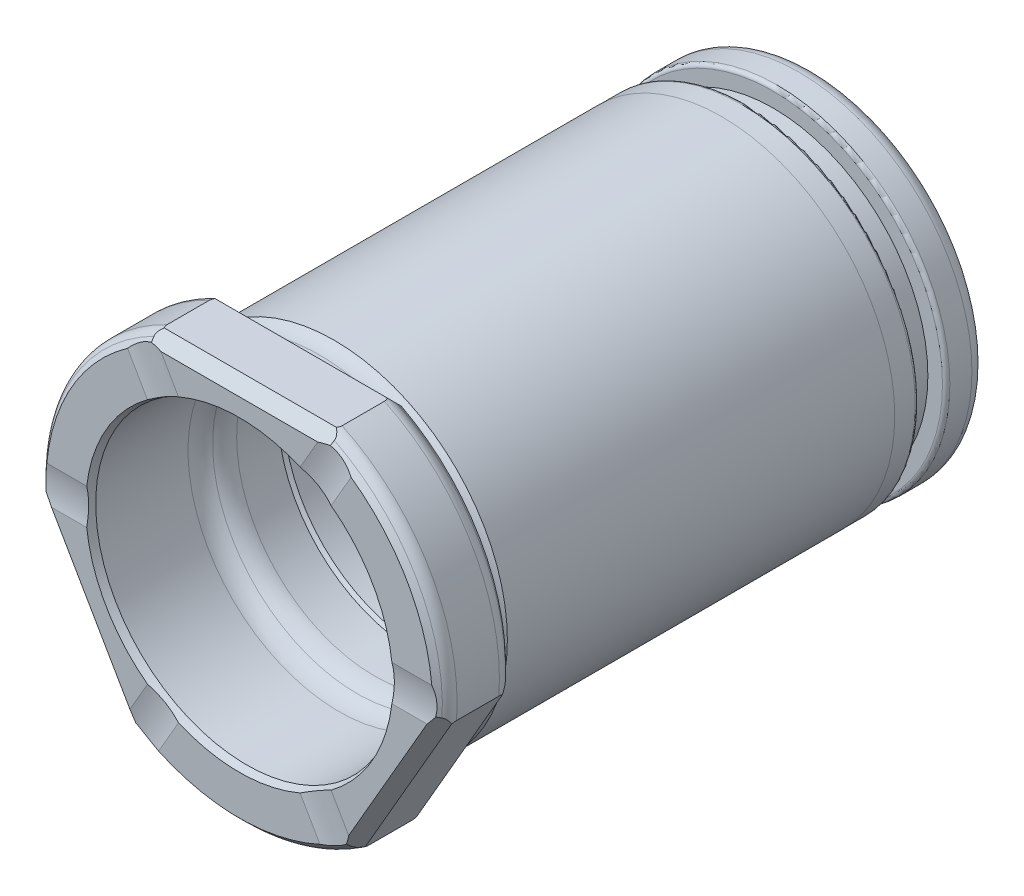
SolidWorks part; units mm, degrees
ref_plane "Front Plane" through (0, 0, 0) normal (0, 0, 1) x (1, 0, 0)
ref_plane "Top Plane" through (0, 0, 0) normal (0, 1, 0) x (1, 0, 0)
ref_plane "Right Plane" through (0, 0, 0) normal (1, 0, 0) x (0, 0, -1)
sketch "Sketch1" plane through (0, 0, 0) normal (1, 0, 0) x (0, 0, -1)
  line L0 (0, 26.25) -> (0, 20.864)
  line L1 (0, 26.25) -> (0.6642, 26.9142)
  line L2 (2.0784, 27.5) -> (7.8216, 27.5)
  line L3 (9.2358, 26.9142) -> (9.9, 26.25)
  line L4 (9.9, 26.25) -> (9.9, 24.6034)
  line L5 (9.9, 24.6034) -> (9.572, 23.3794)
  line L8 (12.9, 23.5) -> (65.5, 23.5)
  line L9 (68.8, 22.98) -> (68.8, 21)
  line L10 (68.8, 21) -> (72.5, 21)
  line L11 (72.5, 21) -> (72.5, 22.98)
  line L12 (73, 23.48) -> (76, 23.48)
  line L13 (78, 21.48) -> (78, 20)
  line L14 (78, 20) -> (78.5, 20)
  line L15 (78.5, 20) -> (78.5, 15.25)
  line L16 (78.5, 15.25) -> (76.55, 15.25)
  line L17 (76.55, 15.25) -> (76, 15.8)
  line L18 (76, 15.8) -> (73.5, 15.8)
  line L19 (73.5, 15.8) -> (73.5, 18.5)
  line L20 (73.5, 18.5) -> (68.5, 18.5)
  line L21 (68.5, 18.5) -> (68.5, 15.15)
  line L22 (68.5, 15.15) -> (65.7, 15.15)
  line L23 (65.7, 15.15) -> (65.7, 18.75)
  line L24 (65.7, 18.75) -> (62.5, 18.75)
  line L25 (62.5, 18.75) -> (62.5, 15.15)
  line L26 (62.5, 15.15) -> (61, 15.15)
  line L27 (61, 15.15) -> (61, 15.8)
  line L28 (61, 15.8) -> (59.5, 15.8)
  line L29 (59.5, 15.8) -> (59.5, 17.9999)
  line L30 (58.9999, 18.5) -> (24.5394, 18.5)
  line L31 (24.5394, 18.5) -> (24, 18.7515)
  line L34 (13.5373, 20.5) -> (1, 20.5)
  line L35 (0, 0) -> (109.6679, 0) construction
  line L37 (65.5, 23.5) -> (65.5, 23.48)
  line L38 (65.5, 23.48) -> (68.3, 23.48)
  line L39 (1, 20.5) -> (0, 20.864)
  line L40 (18.3896, 18.7515) -> (24, 18.7515)
  line L41 (10.055, 22.75) -> (10.9157, 22.75)
  arc A0 (10.055, 22.75) -> (9.572, 23.3794) centre (10.055, 23.25) cw
  arc A3 (58.9999, 18.5) -> (59.5, 17.9999) centre (59.5, 18.5) cw
  arc A4 (7.8216, 27.5) -> (9.2358, 26.9142) centre (7.8216, 25.5) cw
  arc A5 (0.6642, 26.9142) -> (2.0784, 27.5) centre (2.0784, 25.5) cw
  arc A6 (12.9, 23.5) -> (10.9157, 22.75) centre (10.9157, 25.75) cw
  arc A7 (76, 23.48) -> (78, 21.48) centre (76, 21.48) cw
  arc A8 (16.0031, 19.6251) -> (13.5373, 20.5) centre (13.5061, 16.5001) ccw
  arc A9 (16.0031, 19.6251) -> (18.3896, 18.7515) centre (18.5, 22.75) ccw
  arc A10 (68.3, 23.48) -> (68.8, 22.98) centre (68.3, 22.98) cw
  arc A11 (73, 23.48) -> (72.5, 22.98) centre (73, 22.98) ccw
  dimension "D10" = 0.5
  dimension "D40" = 0.5001
  dimension "D42" = 2
  dimension "D43" = 3
  dimension "D7" = 10.055
  dimension "D49" = 13
  dimension "D46" = 2
  dimension "D54" = 18.5
  dimension "D55" = 16.5001
  dimension "D11" = 4
  dimension "D12" = 4
  dimension "D59" = 0.5
  dimension "D60" = 0.5
  dimension "D2" = 20.5
  dimension "D5" = 26.25
  dimension "D6" = 45
  dimension "D8" = 9.9
  dimension "D9" = 45.5
  dimension "D13" = 24
  dimension "D14" = 22.75
  dimension "D15" = 18.5
  dimension "D16" = 59.5
  dimension "D17" = 61
  dimension "D18" = 15.8
  dimension "D19" = 15.15
  dimension "D20" = 62.5
  dimension "D21" = 3.2
  dimension "D22" = 2.8
  dimension "D23" = 5
  dimension "D24" = 23.5
  dimension "D25" = 52.5
  dimension "D26" = 18.75
  dimension "D27" = 21
  dimension "D28" = 18.5
  dimension "D29" = 3.7
  dimension "D30" = 23.48
  dimension "D31" = 20
  dimension "D32" = 0.5
  dimension "D33" = 2.5
  dimension "D34" = 5
  dimension "D35" = 78.5
  dimension "D36" = 15.15
  dimension "D37" = 6
  dimension "D38" = 15.8
  dimension "D39" = 15.25
  dimension "D41" = 18.5
  dimension "D44" = 17.9999
  dimension "D45" = 3
  dimension "D47" = 55
  dimension "D48" = 15
  dimension "D50" = 23.48
  dimension "D51" = 1.5
  dimension "D52" = 1
  dimension "D53" = 20
  dimension "D56" = 18.3896
  dimension "D58" = 25
revolve "Revolve1" add sketch "Sketch1" angle 360 about L35
sketch "Sketch2" plane through (0, 0, 0) normal (1, 0, 0) x (0, 0, -1)
  line L1 (0, 26.25) -> (0, -26.25) construction
  circle A0 centre (-9.7, 0) radius 10
  dimension "D1" = 20
  dimension "D3" = 0.3
  dimension "D2" = 9.7
extrude "Cut-Extrude1" cut sketch "Sketch2" against normal up to next
pattern_circular "CirPattern1" count 6 over 360 about axis through (0, 0, 0) along (0, 0, 1) of "Cut-Extrude1" reverse direction yes
sketch "Sketch3" plane through (0, 0, 0) normal (0, 0, 1) x (1, 0, 0)
  line L1 (-15, 24.8) -> (15, 24.8)
  line L2 (-15, 24.8) -> (-15, 28.8)
  line L3 (-15, 28.8) -> (15, 28.8)
  line L4 (15, 24.8) -> (15, 28.8)
  dimension "D1" = 24.8
  dimension "D2" = 30
  dimension "D3" = 15
  dimension "D4" = 4
extrude "Cut-Extrude2" cut sketch "Sketch3" against normal up to next
pattern_circular "CirPattern2" count 3 over 360 about axis through (0, 0, 0) along (0, 0, 1) of "Cut-Extrude2"
chamfer "Chamfer1" distance 1.5 angle 45 6 edges at (-21.4774, -12.4, -9.9) (21.4774, -12.4, -9.9) (0, 24.8, -9.9) (21.4774, -12.4, 0) (-21.4774, -12.4, 0) (0, 24.8, 0)
